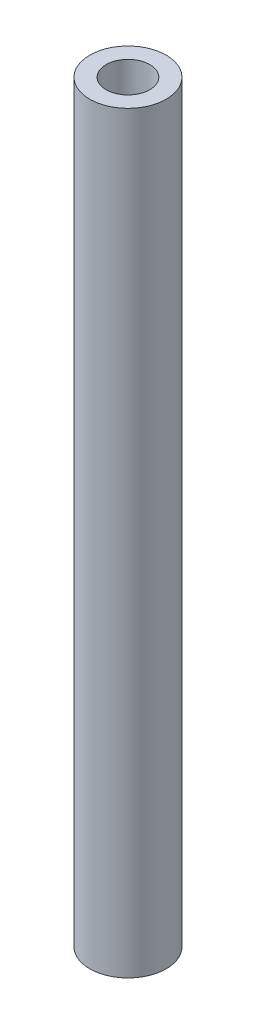
SolidWorks part; units mm, degrees
ref_plane "Plano frontal" through (0, 0, 0) normal (0, 0, 1) x (1, 0, 0)
ref_plane "Plano superior" through (0, 0, 0) normal (0, 1, 0) x (1, 0, 0)
ref_plane "Plano direito" through (0, 0, 0) normal (1, 0, 0) x (0, 0, -1)
ref_plane "Plano1" through (0, 0, 0) normal (0, 0, -1) x (-1, 0, 0)
sketch "Esboço1" plane through (0, 0, 0) normal (0, 0, -1) x (-1, 0, 0)
  line L0 (53.2146, -69) -> (54.7146, -69)
  line L1 (54.7146, -69) -> (54.7146, 0)
  line L2 (54.7146, 0) -> (53.2146, 0)
  line L3 (53.2146, 0) -> (53.2146, -69)
  line L4 (56.7146, -69) -> (56.7146, 0) construction
  dimension "D1" = 2
  dimension "D2" = 3.5
  dimension "D3" = 69
revolve "Revolução1" add sketch "Esboço1" angle 360 about L4 reverse direction yes
